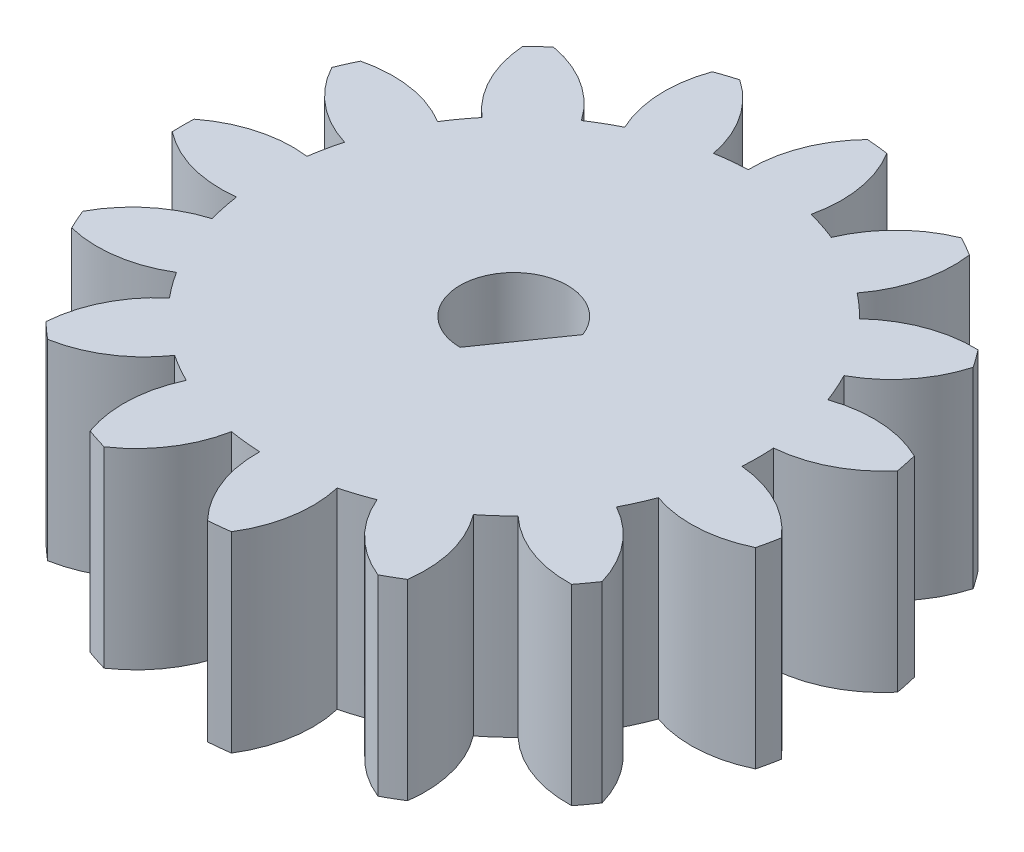
SolidWorks part; units mm, degrees
material "Acrylic (Medium-high impact)"
ref_plane "Front Plane" through (0, 0, 0) normal (0, 0, 1) x (1, 0, 0)
ref_plane "Top Plane" through (0, 0, 0) normal (0, 1, 0) x (1, 0, 0)
ref_plane "Right Plane" through (0, 0, 0) normal (1, 0, 0) x (0, 0, -1)
sketch "Sketch1" plane through (0, 0, 0) normal (0, 1, 0) x (1, 0, 0)
  circle A0 centre (0, 0) radius 56.5317
extrude "Boss-Extrude1" add sketch "Sketch1" along normal blind 5
extrude "Cut-Extrude1" cut sketch "Sketch2" against normal through all contours A74 A73 A72 A71 A70 A18 A19 A20 A21 A13 A12 A11 A10 A25 A24 A23 A22 A29 A28 A27 A26 A33 A32 A31 A30 A37 A36 A35 A34 A41 A40 A39 A38 A45 A44 A43 A42 A49 A48 A47 A46 A53 A52 A51 A50 A57 A56 A55 A54 A61 region at (0, 9.6961, -90.7198)
sketch "Sketch2" plane through (0.054, 9.6961, -2.6905) normal (0, 1, 0) x (0, 0, 1)
  arc A10 (7.0507, 4.4166) -> (7.988, 6.755) centre (4.8627, 6.6506) ccw
  arc A11 (7.988, 6.755) -> (7.5291, 7.0884) centre (2.6905, -0.054) ccw
  arc A12 (7.5291, 7.0884) -> (5.6556, 5.5906) centre (8.3956, 4.0838) ccw
  arc A13 (5.6556, 5.5906) -> (4.7789, 5.9703) centre (2.6905, -0.054) ccw
  arc A18 (3.1034, 6.3087) -> (2.1481, 6.2989) centre (2.6905, -0.054) ccw
  arc A19 (4.2057, 8.4389) -> (3.1034, 6.3087) centre (6.2194, 6.0466) ccw
  arc A20 (4.7605, 8.321) -> (4.2057, 8.4389) centre (2.6905, -0.054) ccw
  arc A21 (4.8554, 5.8036) -> (4.7605, 8.321) centre (1.9479, 6.9545) ccw
  arc A22 (8.4921, 2.2566) -> (10.2994, 4.0116) centre (7.4019, 5.1874) ccw
  arc A23 (10.2994, 4.0116) -> (10.0158, 4.5028) centre (2.6905, -0.054) ccw
  arc A24 (10.0158, 4.5028) -> (7.6951, 3.8966) centre (9.5854, 1.4056) ccw
  arc A25 (7.6951, 3.8966) -> (7.0486, 4.6) centre (2.6905, -0.054) ccw
  arc A26 (8.9303, -0.3029) -> (11.2952, 0.5653) centre (9.1264, 2.818) ccw
  arc A27 (11.2952, 0.5653) -> (11.2359, 1.1294) centre (2.6905, -0.054) ccw
  arc A28 (11.2359, 1.1294) -> (8.8693, 1.5195) centre (9.5829, -1.525) ccw
  arc A29 (8.8693, 1.5195) -> (8.5648, 2.425) centre (2.6905, -0.054) ccw
  arc A30 (8.2896, -2.8193) -> (10.8031, -2.9881) centre (9.7381, -0.0481) ccw
  arc A31 (10.8031, -2.9881) -> (10.9784, -2.4487) centre (2.6905, -0.054) ccw
  arc A32 (10.9784, -2.4487) -> (8.975, -1.1297) centre (8.3887, -4.2012) ccw
  arc A33 (8.975, -1.1297) -> (9.0652, -0.1786) centre (2.6905, -0.054) ccw
  arc A34 (6.6807, -4.8576) -> (8.9083, -6.0342) centre (9.1312, -2.9151) ccw
  arc A35 (8.9083, -6.0342) -> (9.2879, -5.6127) centre (2.6905, -0.054) ccw
  arc A36 (9.2879, -5.6127) -> (7.9942, -3.5929) centre (6.2092, -6.1604) ccw
  arc A37 (7.9942, -3.5929) -> (8.4634, -2.7607) centre (2.6905, -0.054) ccw
  arc A38 (4.3819, -6.0653) -> (5.9384, -8.0462) centre (7.4106, -5.2875) ccw
  arc A39 (5.9384, -8.0462) -> (6.4566, -7.8155) centre (2.6905, -0.054) ccw
  arc A40 (6.4566, -7.8155) -> (6.0962, -5.4441) centre (3.4213, -7.0637) ccw
  arc A41 (6.0962, -5.4441) -> (6.8634, -4.8747) centre (2.6905, -0.054) ccw
  arc A42 (1.7907, -6.2336) -> (2.4068, -8.6763) centre (4.8739, -6.7549) ccw
  arc A43 (2.4068, -8.6763) -> (2.9741, -8.6763) centre (2.6905, -0.054) ccw
  arc A44 (2.9741, -8.6763) -> (3.6094, -6.3634) centre (0.507, -6.7549) ccw
  arc A45 (3.6094, -6.3634) -> (4.5418, -6.1552) centre (2.6905, -0.054) ccw
  arc A46 (-0.645, -5.3334) -> (-1.0757, -7.8155) centre (1.9596, -7.0637) ccw
  arc A47 (-1.0757, -7.8155) -> (-0.5575, -8.0462) centre (2.6905, -0.054) ccw
  arc A48 (-0.5575, -8.0462) -> (0.9637, -6.1917) centre (-2.0297, -5.2875) ccw
  arc A49 (0.9637, -6.1917) -> (1.9001, -6.3808) centre (2.6905, -0.054) ccw
  arc A50 (-2.504, -3.5203) -> (-3.907, -5.6127) centre (-0.8283, -6.1604) ccw
  arc A51 (-3.907, -5.6127) -> (-3.5274, -6.0342) centre (2.6905, -0.054) ccw
  arc A52 (-3.5274, -6.0342) -> (-1.3835, -4.9587) centre (-3.7503, -2.9151) ccw
  arc A53 (-1.3835, -4.9587) -> (-0.6049, -5.5123) centre (2.6905, -0.054) ccw
  arc A54 (-3.4648, -1.1078) -> (-5.5975, -2.4487) centre (-3.0078, -4.2012) ccw
  arc A55 (-5.5975, -2.4487) -> (-5.4222, -2.9881) centre (2.6905, -0.054) ccw
  arc A56 (-5.4222, -2.9881) -> (-3.0262, -2.8776) centre (-4.3572, -0.0481) ccw
  arc A57 (-3.0262, -2.8776) -> (-2.5401, -3.7001) centre (2.6905, -0.054) ccw
  arc A58 (-3.3613, 1.4869) -> (-5.855, 1.1294) centre (-4.202, -1.525) ccw
  arc A59 (-5.855, 1.1294) -> (-5.9143, 0.5653) centre (2.6905, -0.054) ccw
  arc A60 (-5.9143, 0.5653) -> (-3.6805, -0.3083) centre (-3.7455, 2.818) ccw
  arc A61 (-3.6805, -0.3083) -> (-3.5709, -1.2574) centre (2.6905, -0.054) ccw
  arc A62 (-2.2114, 3.8151) -> (-4.6349, 4.5028) centre (-4.2045, 1.4056) ccw
  arc A63 (-4.6349, 4.5028) -> (-4.9185, 4.0116) centre (2.6905, -0.054) ccw
  arc A64 (-4.9185, 4.0116) -> (-3.2331, 2.3049) centre (-2.021, 5.1874) ccw
  arc A65 (-3.2331, 2.3049) -> (-3.5191, 1.3934) centre (2.6905, -0.054) ccw
  arc A66 (-0.2139, 5.4744) -> (-2.1482, 7.0884) centre (-3.0147, 4.0838) ccw
  arc A67 (-2.1482, 7.0884) -> (-2.6071, 6.755) centre (2.6905, -0.054) ccw
  arc A68 (-2.6071, 6.755) -> (-1.7616, 4.5103) centre (0.5182, 6.6506) ccw
  arc A69 (-1.7616, 4.5103) -> (-2.3936, 3.7939) centre (2.6905, -0.054) ccw
  arc A70 (2.2858, 6.1777) -> (1.1752, 8.4389) centre (-0.8385, 6.0466) ccw
  arc A71 (1.1752, 8.4389) -> (0.6204, 8.321) centre (2.6905, -0.054) ccw
  arc A72 (0.6204, 8.321) -> (0.4798, 5.9265) centre (3.433, 6.9545) ccw
  arc A73 (0.4798, 5.9265) -> (-0.389, 5.5291) centre (2.6905, -0.054) ccw
  circle A74 centre (2.6905, -0.054) radius 93.3605
  point P109 (2.6905, -0.054)
extrude "Cut-Extrude2" cut sketch "Sketch4" against normal through all
sketch "Sketch4" plane through (64.694, 5.1354, -48.3581) normal (0, 1, 0) x (1, 0, 0)
  line L3 (-64.694, -49.7581) -> (-63.3809, -47.8724)
  arc A3 (-63.3809, -47.8724) -> (-64.694, -49.7581) centre (-64.694, -48.3581) ccw
